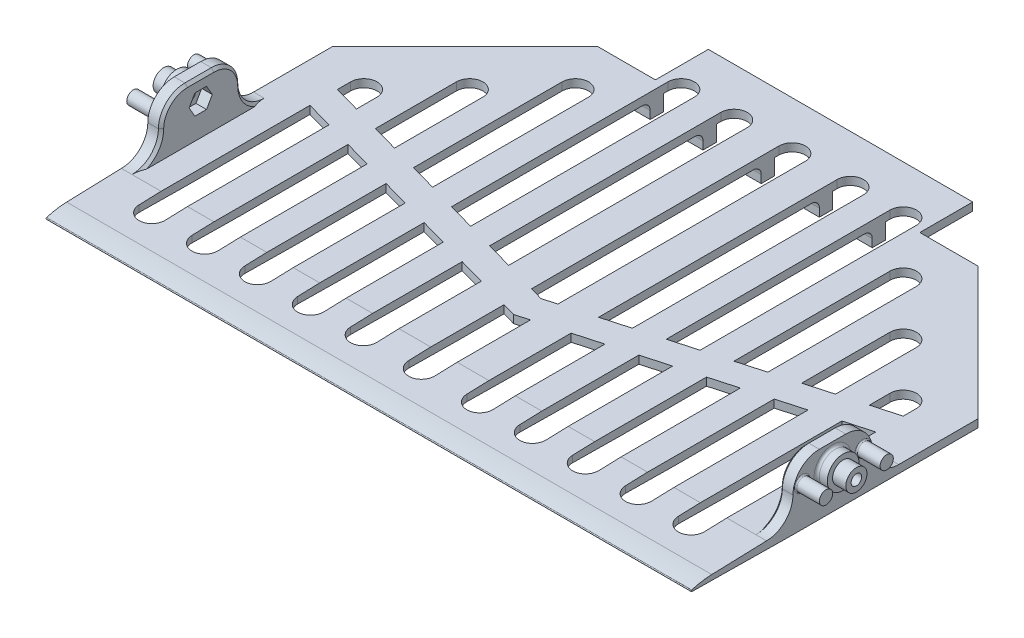
SolidWorks part; units mm, degrees
material "PA Type 6"
ref_plane "Front Plane" through (0, 0, 0) normal (0, 0, 1) x (1, 0, 0)
ref_plane "Top Plane" through (0, 0, 0) normal (0, 1, 0) x (1, 0, 0)
ref_plane "Right Plane" through (0, 0, 0) normal (1, 0, 0) x (0, 0, -1)
sketch "Sketch1" plane through (0, 0, 0) normal (0, 1, 0) x (1, 0, 0)
  line L0 (0, 113.8812) -> (0, -115.6912) construction
  line L1 (-122, -80) -> (122, -80)
  line L2 (-122, -80) -> (-122, 80)
  line L3 (-122, 80) -> (-50, 80)
  line L4 (122, -80) -> (122, 80)
  line L5 (-122, -80) -> (122, 80) construction
  line L6 (-122, 80) -> (122, -80) construction
  line L7 (-50, 80) -> (-50, 100)
  line L8 (-50, 100) -> (50, 100)
  line L9 (50, 80) -> (50, 100)
  line L10 (50, 80) -> (122, 80)
  point P0 (0, 0)
  point P13 (0, 100)
  dimension "D1" = 244
  dimension "D2" = 160
  dimension "D3" = 20
  dimension "D4" = 50
extrude "Boss-Extrude1" add sketch "Sketch1" along normal blind 3
sketch "Sketch2" plane through (0, 3, 0) normal (0, 1, 0) x (1, 0, 0)
  line L0 (-132.9647, 0) -> (140.2961, 0) construction
  line L1 (-132.9647, -25) -> (137.7968, -25) construction
  line L2 (-122, 80) -> (-122, -80) construction
  line L4 (-122, -10) -> (-122, -40)
  line L5 (-122, -10) -> (-117, -10)
  line L6 (-117, -10) -> (-117, -40)
  line L7 (-122, -40) -> (-117, -40)
  line L8 (0, 88.4071) -> (0, -88.8787) construction
  line L9 (122, -10) -> (117, -10)
  line L10 (122, -10) -> (122, -40)
  line L11 (122, -40) -> (117, -40)
  line L12 (117, -10) -> (117, -40)
  point P14 (-117, -25)
  point P15 (-122, -25)
  dimension "D1" = 25
  dimension "D2" = 5
  dimension "D3" = 15
extrude "Boss-Extrude2" add sketch "Sketch2" along normal blind 20
sketch "Sketch3" plane through (-122, 0, 0) normal (-1, 0, 0) x (0, 0, 1)
  line L0 (25, 23) -> (25, 5.4142) construction
  line L1 (10, 23) -> (40, 23) construction
  circle A0 centre (25, 15) radius 6
  dimension "D1" = 12
  dimension "D2" = 8
extrude "Boss-Extrude3" add sketch "Sketch3" along normal blind 4 and the other way blind 244
sketch "Sketch5" plane through (-126, 0, 0) normal (-1, 0, 0) x (0, 0, 1)
  circle A0 centre (25, 15) radius 2
  dimension "D1" = 4
extrude "Cut-Extrude2" cut sketch "Sketch5" against normal through all
fillet "Fillet1" radius 10 8 edges at (119.5, 3, 40) (119.5, 23, 40) (119.5, 3, 10) (119.5, 23, 10) (-119.5, 3, 10) (-119.5, 3, 40) (-119.5, 23, 10) (-119.5, 23, 40)
sketch "Sketch6" plane through (-126, 0, 0) normal (-1, 0, 0) x (0, 0, 1)
  circle A0 centre (25, 15) radius 2
  circle A1 centre (25, 15) radius 4
  dimension "D1" = 8
  dimension "D2" = 4
extrude "Boss-Extrude4" add sketch "Sketch6" along normal blind 5
sketch "Sketch8" plane through (117, 0, 0) normal (-1, 0, 0) x (0, 0, 1)
  line L1 (29.3879, 15) -> (27.1939, 18.8)
  line L2 (27.1939, 18.8) -> (22.8061, 18.8)
  line L3 (22.8061, 18.8) -> (20.6121, 15)
  line L4 (20.6121, 15) -> (22.8061, 11.2)
  line L5 (22.8061, 11.2) -> (27.1939, 11.2)
  line L6 (27.1939, 11.2) -> (29.3879, 15)
  circle A0 centre (25, 15) radius 3.8 construction
  dimension "D1" = 7.6
extrude "Cut-Extrude3" cut sketch "Sketch8" against normal blind 4 and the other way blind 238
sketch "Sketch9" plane through (-122, 0, 0) normal (-1, 0, 0) x (0, 0, 1)
  line L2 (-80, 0) -> (80, 0) construction
  line L3 (40, 0) -> (80, 0)
  line L5 (80, 0) -> (80, 0.5)
  line L6 (80, 3) -> (80, 0) construction
  line L7 (80, 0.5) -> (40, 0)
  line L8 (50, 3) -> (80, 2)
  line L9 (80, 2) -> (80, 3)
  line L10 (80, 3) -> (50, 3)
  dimension "D1" = 40
  dimension "D2" = 0.5
  dimension "D3" = 1
extrude "Cut-Extrude4" cut sketch "Sketch9" against normal through all
fillet "Fillet9" radius 30 1 edges at (0, 2, 80)
fillet "Fillet10" radius 0.3 1 edges at (0, 0.5, 80)
sketch "Sketch12" plane through (0, 3, 0) normal (0, 1, 0) x (1, 0, 0)
  line L0 (0, 94.3328) -> (0, -35.8869) construction
  line L1 (-72, 80) -> (-122, 30)
  line L2 (-50, 80) -> (-122, 80) construction
  line L3 (-122, 80) -> (-122, 0) construction
  line L4 (-72, 80) -> (-122, 80)
  line L5 (-122, 80) -> (-122, 30)
  line L6 (72, 80) -> (122, 80)
  line L7 (72, 80) -> (122, 30)
  line L8 (122, 80) -> (122, 30)
  dimension "D1" = 50
  dimension "D2" = 50
extrude "Cut-Extrude6" cut sketch "Sketch12" against normal through all
sketch "Sketch13" plane through (122, 0, 0) normal (1, 0, 0) x (0, 0, -1)
  circle A0 centre (-25, 15) radius 6
  circle A1 centre (-25, 15) radius 2
  dimension "D1" = 12
  dimension "D2" = 4
extrude "Boss-Extrude7" add sketch "Sketch13" along normal blind 4
sketch "Sketch14" plane through (126, 0, 0) normal (1, 0, 0) x (0, 0, -1)
  circle A0 centre (-25, 15) radius 2
  circle A1 centre (-25, 15) radius 4
  dimension "D1" = 4
  dimension "D2" = 8
extrude "Boss-Extrude8" add sketch "Sketch14" along normal blind 5
fillet "Fillet11" radius 1 2 edges at (122, 15, 31) (-122, 15, 19)
sketch "Sketch15" plane through (0, 0, 0) normal (0, -1, 0) x (1, 0, 0)
  line L0 (-72, -80) -> (-72, -75)
  line L1 (-72, -75) -> (72, -75)
  line L2 (72, -75) -> (72, -80)
  line L3 (72, -80) -> (-72, -80)
  dimension "D1" = 5
extrude "Boss-Extrude9" add sketch "Sketch15" along normal blind 6
fillet "Fillet12" radius 3 1 edges at (0, 0, -75)
sketch "Sketch16" plane through (-122, 0, 0) normal (-1, 0, 0) x (0, 0, 1)
  line L0 (25, 15) -> (43.4691, 15) construction
  line L1 (25, 15) -> (8.4379, 15) construction
  circle A0 centre (36.48, 15) radius 2.5
  circle A1 centre (13.52, 15) radius 2.5
  dimension "D1" = 5
  dimension "D2" = 5
  dimension "D3" = 11.48
  dimension "D4" = 11.48
extrude "Boss-Extrude10" add sketch "Sketch16" along normal blind 9 and the other way blind 253
fillet "Fillet13" radius 0.5 4 edges at (122, 15, 16.02) (122, 15, 38.98) (-122, 15, 33.98) (-122, 15, 11.02)
sketch "Sketch17" plane through (0, 0, 0) normal (0, 0, 1) x (1, 0, 0)
  line L0 (-117, 27.464) -> (-117, 4.9987)
  line L1 (-117, 3) -> (-117, 13) construction
  line L2 (-117, 4.9987) -> (117, 4.9987)
  line L3 (117, 13) -> (117, 3) construction
  line L4 (117, 4.9987) -> (117, 27.464)
  line L5 (117, 27.464) -> (-117, 27.464)
extrude "Cut-Extrude7" cut sketch "Sketch17" against normal through all both and the other way through all
chamfer "Chamfer1" distance 1 angle 45 10 edges at (117, 5.9289, 7.0711) (117, 20.0711, 12.9289) (117, 5.9289, 42.9289) (117, 23, 25) (117, 20.0711, 37.0711) (-117, 5.9289, 7.0711) (-117, 20.0711, 12.9289) (-117, 23, 25) (-117, 5.9289, 42.9289) (-117, 20.0711, 37.0711)
sketch "Sketch18" plane through (0, 3, 0) normal (0, 1, 0) x (1, 0, 0)
  line L0 (0, 113.2415) -> (0, -97.94) construction
  line L1 (-126.1981, -2.4824) -> (-25.8823, 97.8334) construction
  line L2 (-122, 30) -> (-72, 80) construction
  line L3 (-102, 58.4907) -> (-102, -90.3004) construction
  line L4 (-122, 30) -> (-122, 0) construction
  line L5 (-129.7336, -58.3001) -> (0, -58.3001) construction
  line L6 (-122, -78.3001) -> (122, -78.3001) construction
  line L7 (-102, 21.7157) -> (-102, -58.3001) construction
  line L8 (-97, 21.7157) -> (-97, -58.3001)
  line L9 (-107, 21.7157) -> (-107, -58.3001)
  line L10 (-82, 41.7157) -> (-82, -58.3001) construction
  line L11 (-77, 41.7157) -> (-77, -58.3001)
  line L12 (-87, 41.7157) -> (-87, -58.3001)
  line L13 (-62, 61.7157) -> (-62, -58.3001) construction
  line L14 (-57, 61.7157) -> (-57, -58.3001)
  line L15 (-67, 61.7157) -> (-67, -58.3001)
  line L16 (-42, 81.7157) -> (-42, -58.3001) construction
  line L17 (-37, 81.7157) -> (-37, -58.3001)
  line L18 (-47, 81.7157) -> (-47, -58.3001)
  line L19 (-22, 81.7157) -> (-22, -58.3001) construction
  line L20 (-17, 81.7157) -> (-17, -58.3001)
  line L21 (-27, 81.7157) -> (-27, -58.3001)
  line L22 (-42, 81.7157) -> (9.6984, 81.7157) construction
  line L23 (102, 21.7157) -> (102, -58.3001) construction
  line L24 (97, 21.7157) -> (97, -58.3001)
  line L25 (107, 21.7157) -> (107, -58.3001)
  line L26 (82, 41.7157) -> (82, -58.3001) construction
  line L27 (77, 41.7157) -> (77, -58.3001)
  line L28 (87, 41.7157) -> (87, -58.3001)
  line L29 (62, 61.7157) -> (62, -58.3001) construction
  line L30 (57, 61.7157) -> (57, -58.3001)
  line L31 (67, 61.7157) -> (67, -58.3001)
  line L32 (42, 81.7157) -> (42, -58.3001) construction
  line L33 (37, 81.7157) -> (37, -58.3001)
  line L34 (47, 81.7157) -> (47, -58.3001)
  line L35 (22, 81.7157) -> (22, -58.3001) construction
  line L36 (17, 81.7157) -> (17, -58.3001)
  line L37 (27, 81.7157) -> (27, -58.3001)
  line L38 (0, 81.7157) -> (0, -58.3001) construction
  line L39 (5, 81.7157) -> (5, -58.3001)
  line L40 (-5, 81.7157) -> (-5, -58.3001)
  arc A0 (-97, 21.7157) -> (-107, 21.7157) centre (-102, 21.7157) ccw
  arc A1 (-107, -58.3001) -> (-97, -58.3001) centre (-102, -58.3001) ccw
  arc A2 (-77, 41.7157) -> (-87, 41.7157) centre (-82, 41.7157) ccw
  arc A3 (-87, -58.3001) -> (-77, -58.3001) centre (-82, -58.3001) ccw
  arc A4 (-57, 61.7157) -> (-67, 61.7157) centre (-62, 61.7157) ccw
  arc A5 (-67, -58.3001) -> (-57, -58.3001) centre (-62, -58.3001) ccw
  arc A6 (-37, 81.7157) -> (-47, 81.7157) centre (-42, 81.7157) ccw
  arc A7 (-47, -58.3001) -> (-37, -58.3001) centre (-42, -58.3001) ccw
  arc A8 (-17, 81.7157) -> (-27, 81.7157) centre (-22, 81.7157) ccw
  arc A9 (-27, -58.3001) -> (-17, -58.3001) centre (-22, -58.3001) ccw
  arc A10 (97, 21.7157) -> (107, 21.7157) centre (102, 21.7157) cw
  arc A11 (107, -58.3001) -> (97, -58.3001) centre (102, -58.3001) cw
  arc A12 (77, 41.7157) -> (87, 41.7157) centre (82, 41.7157) cw
  arc A13 (87, -58.3001) -> (77, -58.3001) centre (82, -58.3001) cw
  arc A14 (57, 61.7157) -> (67, 61.7157) centre (62, 61.7157) cw
  arc A15 (67, -58.3001) -> (57, -58.3001) centre (62, -58.3001) cw
  arc A16 (37, 81.7157) -> (47, 81.7157) centre (42, 81.7157) cw
  arc A17 (47, -58.3001) -> (37, -58.3001) centre (42, -58.3001) cw
  arc A18 (17, 81.7157) -> (27, 81.7157) centre (22, 81.7157) cw
  arc A19 (27, -58.3001) -> (17, -58.3001) centre (22, -58.3001) cw
  arc A20 (5, 81.7157) -> (-5, 81.7157) centre (0, 81.7157) ccw
  arc A21 (-5, -58.3001) -> (5, -58.3001) centre (0, -58.3001) ccw
  point P17 (-102, -18.2922)
  point P24 (-82, -8.2922)
  point P31 (-62, 1.7078)
  point P36 (-42, 11.7078)
  point P43 (-22, 11.7078)
  point P55 (102, -18.2922)
  point P62 (82, -8.2922)
  point P69 (62, 1.7078)
  point P76 (42, 11.7078)
  point P83 (22, 11.7078)
  point P88 (0, 11.7078)
  point P93 (0, 81.7157)
  point P94 (9.6984, 81.7157)
  point P95 (0, 81.7157)
  dimension "D4" = 5
  dimension "D5" = 5
  dimension "D7" = 5
  dimension "D8" = 5
  dimension "D9" = 5
  dimension "D13" = 5
  dimension "D1" = 20
  dimension "D2" = 20
  dimension "D3" = 20
  dimension "D6" = 20
  dimension "D10" = 20
  dimension "D11" = 20
  dimension "D12" = 20
extrude "Cut-Extrude8" cut sketch "Sketch18" against normal through all
sketch "Sketch19" plane through (0, 3, 0) normal (0, 1, 0) x (1, 0, 0)
  line L0 (-107, 16.7157) -> (0, -13.2843)
  line L1 (-107, 21.7157) -> (-107, -50) construction
  line L2 (0, -13.2843) -> (107, 16.7157)
  line L3 (107, -50) -> (107, 21.7157) construction
  line L4 (0, 0) -> (0, -23.1623) construction
  line L5 (-107, 6.3301) -> (0, -23.6699)
  line L6 (0, -23.6699) -> (107, 6.3301)
  line L7 (-107, 16.7157) -> (-107, 6.3301)
  line L8 (107, 16.7157) -> (107, 6.3301)
  line L10 (-109.6996, 7.087) -> (0, -23.6699) construction
  line L11 (0, -23.6699) -> (109.6996, 7.087) construction
  arc A0 (5, 81.7157) -> (-5, 81.7157) centre (0, 81.7157) ccw construction
  arc A1 (107, 21.7157) -> (97, 21.7157) centre (102, 21.7157) ccw construction
  dimension "D1" = 95
  dimension "D2" = 5
  dimension "D3" = 5
  dimension "D4" = 10
extrude "Boss-Extrude11" add sketch "Sketch19" against normal blind 3
